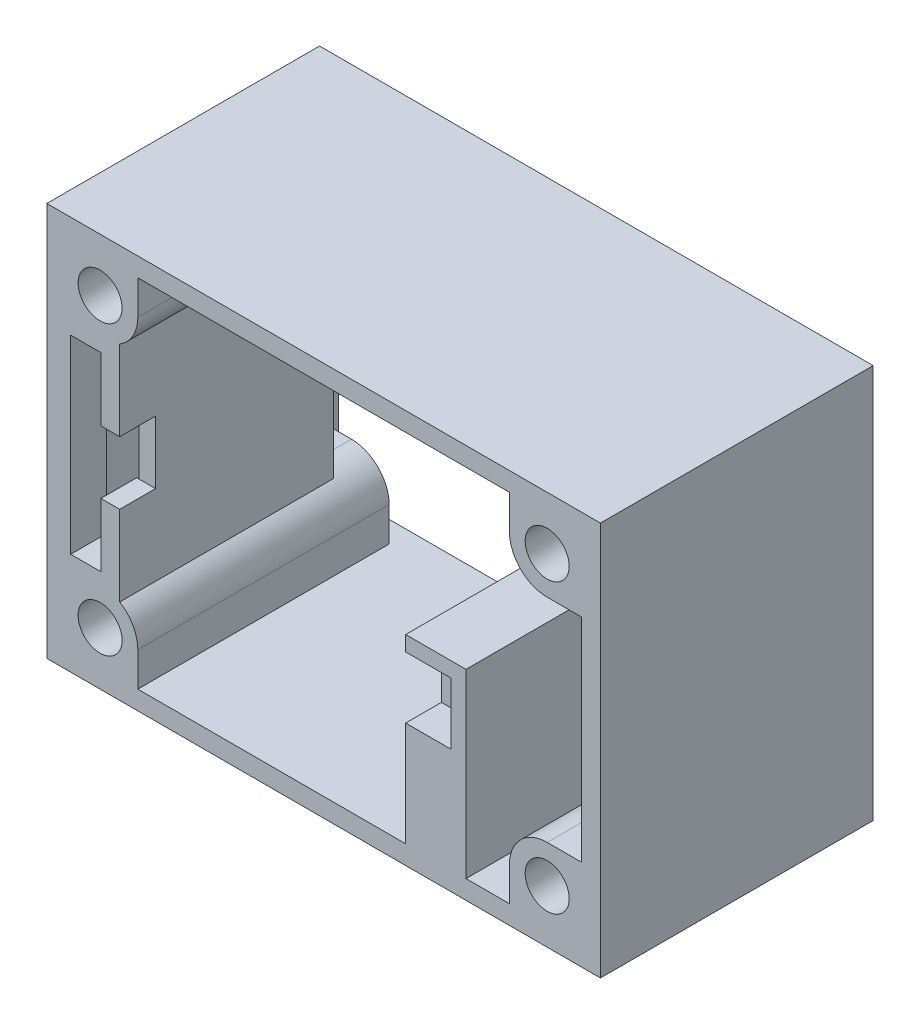
SolidWorks part; units mm, degrees
ref_plane "Front Plane" through (0, 0, 0) normal (0, 0, 1) x (1, 0, 0)
ref_plane "Top Plane" through (0, 0, 0) normal (0, 1, 0) x (1, 0, 0)
ref_plane "Right Plane" through (0, 0, 0) normal (1, 0, 0) x (0, 0, -1)
sketch "Sketch1" plane through (0, 0, 0) normal (0, 0, 1) x (1, 0, 0)
  line L0 (-20.325, 13.975) -> (-20.325, 14.175) construction
  line L1 (-22.025, -15.675) -> (22.025, -15.675)
  line L2 (-22.025, -15.675) -> (-22.025, 15.675)
  line L3 (-22.025, 15.675) -> (22.025, 15.675)
  line L4 (20.325, -13.975) -> (20.325, 13.975)
  line L5 (20.325, 13.975) -> (-20.325, 13.975)
  line L6 (-20.325, 13.975) -> (-20.325, -13.975)
  line L7 (-20.325, -13.975) -> (20.325, -13.975)
  line L8 (20.325, -13.975) -> (20.325, 13.975)
  line L9 (20.325, 13.975) -> (-20.325, 13.975)
  line L10 (-20.325, 13.975) -> (-20.325, -13.975)
  line L11 (-20.325, -13.975) -> (20.325, -13.975)
  line L12 (22.025, -15.675) -> (22.025, 15.675)
  line L13 (-22.025, -15.675) -> (22.025, 15.675) construction
  line L14 (-22.025, 15.675) -> (22.025, -15.675) construction
  line L15 (-20.325, 13.975) -> (-20.525, 13.975) construction
  line L16 (-14.7875, 11.45) -> (-14.7875, 14.175)
  line L17 (-17.7875, 8.45) -> (-20.525, 8.45)
  line L18 (0, 15.675) -> (0, -15.675) construction
  line L19 (-22.025, 0) -> (22.025, 0) construction
  line L20 (14.7875, 11.45) -> (14.7875, 14.175)
  line L21 (17.7875, 8.45) -> (20.525, 8.45)
  line L22 (17.7875, -8.45) -> (20.525, -8.45)
  line L23 (14.7875, -11.45) -> (14.7875, -14.175)
  line L24 (-14.7875, -11.45) -> (-14.7875, -14.175)
  line L25 (-17.7875, -8.45) -> (-20.525, -8.45)
  line L26 (-20.525, 14.175) -> (-22.025, 14.175) construction
  line L27 (20.525, -14.175) -> (-20.525, -14.175)
  line L28 (20.525, -14.175) -> (20.525, 14.175)
  line L29 (20.525, 14.175) -> (-20.525, 14.175)
  line L30 (-20.525, -14.175) -> (-20.525, 14.175)
  line L31 (20.525, -14.175) -> (-20.525, 14.175) construction
  line L32 (20.525, 14.175) -> (-20.525, -14.175) construction
  line L33 (-20.525, 14.175) -> (-20.525, 15.675) construction
  circle A0 centre (-17.7875, 11.45) radius 1.75
  circle A1 centre (17.7875, 11.45) radius 3
  circle A2 centre (17.7875, -11.45) radius 3
  circle A3 centre (-17.7875, -11.45) radius 3
  circle A4 centre (-17.7875, 11.45) radius 3
  circle A5 centre (17.7875, 11.45) radius 1.75
  circle A6 centre (17.7875, -11.45) radius 1.75
  circle A7 centre (-17.7875, -11.45) radius 1.75
  point P9 (0, 0)
  point P16 (0, 0)
  point P44 (-19.0562, -8.45)
  dimension "D2" = 3.5
  dimension "D4" = 6
  dimension "D3" = 1.5
  dimension "D5" = 0.2
  dimension "D1" = 0
extrude "Boss-Extrude1" add sketch "Sketch1" along normal blind 20 contours A4 L16 L9 | A4 L9 L16 L29 | L1 L12 L3 L2 A4 L29 A1 L28 A2 L27 A3 L30 | L29 A4 | A4 L29 L30 L10 L9 | A4 L9 L10 | L9 A4 L29 | L30 A4 | L10 A4 L30 | L9 A4 L10 A0 | A4 L30 L17 L10 | A4 L10 L17 | A1 L29 | L29 A1 L9 L8 L28 | L9 A1 L8 | A1 L8 L9 A5 | A1 L9 L29 | A1 L28 L8 | A1 L28 | L8 A1 L21 | L28 A1 L8 L21 | L20 A1 L9 | L9 A1 L29 L20 | A2 L28 L22 L8 | A2 L8 L22 | L8 A2 L11 A6 | L28 A2 | L28 A2 L8 | A2 L27 L28 L8 L11 | A2 L11 L8 | L11 A2 L27 | L27 A2 | A2 L23 L11 | A2 L11 L23 L27 | L27 A3 L11 L10 L30 | L11 A3 L10 | A3 L10 L30 | A3 L30 | L30 A3 L10 L25 | L10 A3 L25 | A3 L11 L10 A7 | A3 L11 L27 | A3 L27 | L24 A3 L11 | L11 A3 L27 L24 region at (-21.4843, 0, 0) region at (20.042, -13.6898, 0) region at (20.3461, -13.5127, 0) region at (19.8615, -13.508, 0) region at (20.4207, -11.45, 0) region at (17.7875, -14.0708, 0) region at (19.724, -8.8454, 0) region at (20.4289, -9.2415, 0) region at (20.6304, -11.45, 0) region at (15.5674, -14.0789, 0) region at (15.1778, -13.3764, 0) region at (17.7875, -14.2854, 0) region at (19.724, 8.8454, 0) region at (20.4289, 9.2415, 0) region at (-15.5674, -14.0789, 0) region at (-15.1778, -13.3764, 0) region at (19.1987, 8.8916, 0) region at (20.4207, 11.45, 0) region at (-17.7875, -14.0708, 0) region at (-17.7875, -13.8968, 0) region at (20.042, 13.6898, 0) region at (20.3461, 13.5127, 0) region at (20.6304, 11.45, 0) region at (15.1778, 13.3764, 0) region at (-19.2385, -14.0998, 0) region at (-20.042, -13.6898, 0) region at (-17.7875, -14.2854, 0) region at (-19.724, -8.8454, 0) region at (17.7875, 14.0708, 0) region at (15.5674, 14.0789, 0) region at (-20.4207, -11.45, 0) region at (-20.4289, -9.2415, 0) region at (17.7875, 14.2854, 0) region at (-15.1778, 13.3764, 0) region at (-15.5674, 14.0789, 0) region at (-20.6304, -11.45, 0) region at (-20.4289, 9.2415, 0) region at (-19.724, 8.8454, 0) region at (-15.2237, 12.8512, 0) region at (-17.7875, 14.0708, 0) region at (-20.4207, 11.45, 0) region at (-20.042, 13.6898, 0) region at (-19.8662, 13.9961, 0) region at (-17.7875, 14.2854, 0) region at (-20.6304, 11.45, 0)
sketch "Sketch2" plane through (0, 0, 0) normal (0, 0, -1) x (-1, 0, 0)
  line L0 (-14.7875, 14.175) -> (14.7875, 14.175) construction
  line L2 (-20.525, 14.175) -> (20.525, 14.175)
  line L3 (-20.525, 14.175) -> (-20.525, -14.175)
  line L4 (-20.525, -14.175) -> (20.525, -14.175)
  line L5 (-22.025, -15.675) -> (22.025, -15.675)
  line L6 (22.025, -15.675) -> (22.025, 15.675)
  line L7 (22.025, 15.675) -> (-22.025, 15.675)
  line L8 (-22.025, 15.675) -> (-22.025, -15.675)
  line L9 (-22.025, -15.675) -> (22.025, -15.675)
  line L10 (22.025, -15.675) -> (22.025, 15.675)
  line L11 (22.025, 15.675) -> (-22.025, 15.675)
  line L12 (-22.025, 15.675) -> (-22.025, -15.675)
  line L13 (20.525, 14.175) -> (20.525, -14.175)
  line L14 (-20.525, -8.45) -> (-20.525, 8.45) construction
  line L15 (20.525, -8.45) -> (20.525, 8.45) construction
  line L16 (-14.7875, -14.175) -> (14.7875, -14.175) construction
  line L17 (0, 14.175) -> (0, -14.175) construction
  line L18 (-20.525, 0) -> (20.525, 0) construction
  line L19 (1.5, -14.925) -> (1.5, -14.175)
  line L20 (-1.5, 14.925) -> (1.5, 14.925)
  line L21 (-1.5, 14.925) -> (-1.5, 14.175)
  line L22 (-1.5, 14.175) -> (1.5, 14.175)
  line L23 (1.5, 14.925) -> (1.5, 14.175)
  line L24 (-1.5, 14.925) -> (1.5, 14.175) construction
  line L25 (-1.5, 14.175) -> (1.5, 14.925) construction
  line L26 (-21.275, -1.5) -> (-20.525, -1.5)
  line L27 (-21.275, -1.5) -> (-21.275, 1.5)
  line L28 (-21.275, 1.5) -> (-20.525, 1.5)
  line L29 (-20.525, -1.5) -> (-20.525, 1.5)
  line L30 (-21.275, -1.5) -> (-20.525, 1.5) construction
  line L31 (-21.275, 1.5) -> (-20.525, -1.5) construction
  line L32 (-1.5, -14.925) -> (1.5, -14.925)
  line L33 (-1.5, -14.925) -> (-1.5, -14.175)
  line L34 (21.275, 1.5) -> (20.525, 1.5)
  line L35 (21.275, -1.5) -> (21.275, 1.5)
  line L36 (21.275, -1.5) -> (20.525, -1.5)
  point P20 (0, 14.55)
  point P25 (-20.9, 0)
  line M25 (-22.025, -15.675) -> (22.025, -15.675)
  line M26 (22.025, -15.675) -> (22.025, 15.675)
  line M27 (22.025, 15.675) -> (-22.025, 15.675)
  line M28 (-22.025, 15.675) -> (-22.025, -15.675)
  line M36 (20.525, 8.45) -> (20.525, -8.45)
  line M41 (-14.7875, 14.175) -> (14.7875, 14.175)
  line M62 (14.7875, -14.175) -> (-14.7875, -14.175)
  line M63 (-20.525, -8.45) -> (-20.525, 8.45)
  dimension "D2" = 0.75
  dimension "D3" = 3
  dimension "D1" = 0
extrude "Boss-Extrude2" add sketch "Sketch2" along normal blind 1.7 contours L35 L36 L13 L4 L19 L32 L33 L3 L26 L27 L28 L2 L21 L20 L23 L34 M28 M25 M26 M27 M36 M62 M63 M41 region at (21.4843, 0, 0)
ref_plane "Plane1" through (0, 0, 3) normal (0, 0, -1) x (-1, 0, 0)
sketch "Sketch3" plane through (0, 0, 3) normal (0, 0, -1) x (-1, 0, 0)
  line L0 (-20.525, 0) -> (20.525, 0) construction
  line L1 (-20.525, -1.5) -> (-20.525, 1.5) construction
  line L2 (20.525, -1.5) -> (20.525, 1.5) construction
  line L4 (-20.525, -8.45) -> (-20.525, 8.45) construction
  line L33 (20.525, 14.175) -> (20.525, 1.5) construction
  line L34 (16.225, -8.45) -> (20.525, -8.45)
  line L35 (16.225, -8.45) -> (16.225, 8.45)
  line L36 (16.225, 8.45) -> (20.525, 8.45)
  line L37 (20.525, -8.45) -> (20.525, 8.45)
  line L38 (16.225, -8.45) -> (20.525, 8.45) construction
  line L39 (16.225, 8.45) -> (20.525, -8.45) construction
  line L40 (17.7875, 8.45) -> (20.525, 8.45) construction
  line L41 (16.225, 8.45) -> (16.225, 8.889)
  line L42 (16.225, -8.45) -> (16.225, -8.889)
  line L43 (-8.925, 14.175) -> (-8.925, -14.175) construction
  line L44 (20.325, -7.75) -> (17.525, -7.75)
  line L45 (20.325, -7.75) -> (20.325, 7.75)
  line L46 (20.325, 7.75) -> (17.525, 7.75)
  line L47 (17.525, -7.75) -> (17.525, 7.75)
  line L48 (20.325, -7.75) -> (17.525, 7.75) construction
  line L49 (20.325, 7.75) -> (17.525, -7.75) construction
  line L50 (-20.525, 14.175) -> (-1.5, 14.175) construction
  line L51 (-1.5, -14.175) -> (-20.525, -14.175) construction
  line L52 (-10.325, -0.755) -> (-10.325, 0.245) construction
  line L53 (-6.525, 0.245) -> (-11.325, 0.245)
  line L54 (-6.525, 0.245) -> (-6.525, -14.175)
  line L55 (-6.525, -14.175) -> (-11.325, -14.175)
  line L56 (-11.325, 0.245) -> (-11.325, -14.175)
  line L57 (-6.525, 0.245) -> (-11.325, -14.175) construction
  line L58 (-6.525, -14.175) -> (-11.325, 0.245) construction
  line L59 (-10.325, -0.755) -> (-7.525, -0.755)
  line L60 (-10.325, -0.755) -> (-10.325, -6.055)
  line L61 (-10.325, -6.055) -> (-7.525, -6.055)
  line L62 (-7.525, -0.755) -> (-7.525, -6.055)
  line L63 (-10.325, -0.755) -> (-7.525, -6.055) construction
  line L64 (-10.325, -6.055) -> (-7.525, -0.755) construction
  line L65 (-10.325, -0.755) -> (-11.325, -0.755) construction
  arc A0 (-17.7875, 8.45) -> (-14.7875, 11.45) centre (-17.7875, 11.45) ccw construction
  arc A1 (-14.7875, -11.45) -> (-17.7875, -8.45) centre (-17.7875, -11.45) ccw construction
  arc A2 (-17.7875, 8.45) -> (-14.7875, 11.45) centre (-17.7875, 11.45) ccw
  arc A3 (-14.7875, -11.45) -> (-17.7875, -8.45) centre (-17.7875, -11.45) ccw
  arc A4 (14.7875, 11.45) -> (17.7875, 8.45) centre (17.7875, 11.45) ccw construction
  arc A5 (17.7875, -8.45) -> (14.7875, -11.45) centre (17.7875, -11.45) ccw construction
  arc A6 (17.7875, -8.45) -> (14.7875, -11.45) centre (17.7875, -11.45) ccw
  arc A7 (14.7875, 11.45) -> (17.7875, 8.45) centre (17.7875, 11.45) ccw
  point P41 (18.375, 0)
  point P58 (18.925, 0)
  point P71 (-8.925, -6.965)
  point P76 (-8.925, -3.405)
  dimension "D2" = 0.2
  dimension "D3" = 10.2
  dimension "D4" = 8.12
  dimension "D6" = 4.3
  dimension "D7" = 15.5
  dimension "D8" = 2.8
  dimension "D9" = 1
  dimension "D10" = 5.3
extrude "Boss-Extrude3" add sketch "Sketch3" against normal blind 14.15 contours A2 | A3 | L44 L47 L46 L37 L36 L35 L34 | A7 L41 L36 | A6 L34 L42 | L53 L56 L55 L54 L59 L62 L61 L60 region at (-16.3994, 0, 3) region at (-16.6097, -8.5799, 3) region at (-16.6097, 8.5799, 3) region at (8.925, -7.9366, 3)
sketch "Sketch4" plane through (0, 0, 17.15) normal (0, 0, 1) x (1, 0, 0)
  line L18 (11.325, 0.245) -> (6.525, 0.245)
  line L20 (-20.525, -8.45) -> (-17.7875, -8.45)
  line L21 (-16.225, -8.889) -> (-16.225, 8.889)
  line L22 (-17.7875, 8.45) -> (-20.525, 8.45)
  line L23 (-20.525, 8.45) -> (-20.525, -8.45)
  line L24 (-20.525, -8.45) -> (-17.7875, -8.45)
  line L25 (-16.225, -8.889) -> (-16.225, 8.889)
  line L26 (-17.7875, 8.45) -> (-20.525, 8.45)
  line L27 (-20.525, 8.45) -> (-20.525, -8.45)
  line L33 (-20.125, -7.55) -> (-17.725, -7.55)
  line L34 (-20.125, 7.55) -> (-20.125, -7.55)
  line L35 (11.325, -14.175) -> (11.325, 0.245)
  line L36 (6.525, -14.175) -> (11.325, -14.175)
  line L37 (6.525, 0.245) -> (6.525, -14.175)
  line L38 (11.325, 0.245) -> (6.525, 0.245)
  line L39 (11.325, -14.175) -> (11.325, 0.245)
  line L40 (6.525, -14.175) -> (11.325, -14.175)
  line L41 (6.525, 0.245) -> (6.525, -14.175)
  line L42 (-17.725, 7.55) -> (-20.125, 7.55)
  line L43 (-17.725, -7.55) -> (-17.725, 7.55)
  line L44 (-20.125, -7.55) -> (-17.725, -7.55)
  line L45 (-20.125, 7.55) -> (-20.125, -7.55)
  line L46 (7.725, -5.855) -> (10.125, -5.855)
  line L47 (7.725, -0.955) -> (7.725, -5.855)
  line L48 (10.125, -5.855) -> (10.125, -0.955)
  line L49 (10.125, -0.955) -> (7.725, -0.955)
  line L50 (7.725, -5.855) -> (10.125, -5.855)
  line L51 (7.725, -0.955) -> (7.725, -5.855)
  line L52 (10.125, -5.855) -> (10.125, -0.955)
  line L53 (10.125, -0.955) -> (7.725, -0.955)
  line L54 (-17.725, 7.55) -> (-20.125, 7.55)
  line L55 (-17.725, -7.55) -> (-17.725, 7.55)
  arc A2 (-16.225, -8.889) -> (-17.7875, -8.45) centre (-17.7875, -11.45) ccw
  arc A3 (-17.7875, 8.45) -> (-16.225, 8.889) centre (-17.7875, 11.45) ccw
  arc A4 (-16.225, -8.889) -> (-17.7875, -8.45) centre (-17.7875, -11.45) ccw
  arc A5 (-17.7875, 8.45) -> (-16.225, 8.889) centre (-17.7875, 11.45) ccw
  line M100 (-20.525, -8.45) -> (-17.7875, -8.45)
  arc M101 (-17.7875, -8.45) -> (-16.225, -8.889) centre (-17.7875, -11.45) cw
  line M102 (-16.225, -8.889) -> (-16.225, 8.889)
  arc M103 (-16.225, 8.889) -> (-17.7875, 8.45) centre (-17.7875, 11.45) cw
  line M104 (-17.7875, 8.45) -> (-20.525, 8.45)
  line M105 (-20.525, 8.45) -> (-20.525, -8.45)
  line M106 (-17.525, -7.75) -> (-20.325, -7.75)
  line M107 (-20.325, -7.75) -> (-20.325, 7.75)
  line M108 (-20.325, 7.75) -> (-17.525, 7.75)
  line M109 (-17.525, 7.75) -> (-17.525, -7.75)
  dimension "D1" = 0
  dimension "D2" = 0.2
  dimension "D3" = 0
  dimension "D4" = 0.2
extrude "Boss-Extrude4" add sketch "Sketch4" along normal up to surface (2.85 mm away) contours L38 L41 L40 L39 L53 L52 L50 L51 | M105 M100 M101 M102 M103 M104 M109 M106 M107 M108 | L55 L44 L45 L54 M106 M109 M108 M107 region at (8.925, -7.6937, 17.15) region at (-20.3421, 0, 17.15) region at (-18.925, -7.5925, 17.15) up to face at (0, 0, 20)
sketch "Sketch5" plane through (0, 0, 20) normal (0, 0, 1) x (1, 0, 0)
  line L0 (-16.225, 0) -> (-22.025, 0) construction
  line L1 (-16.225, -8.889) -> (-16.225, 8.889) construction
  line L2 (-22.025, -15.675) -> (-22.025, 15.675) construction
  line L3 (7.725, -3.405) -> (6.525, -3.405) construction
  line L4 (7.725, -0.955) -> (7.725, -5.855) construction
  line L5 (6.525, 0.245) -> (6.525, -14.175) construction
  line L6 (-17.725, -7.55) -> (-17.725, 7.55) construction
  line L7 (-17.725, -2.5) -> (-16.225, -2.5)
  line L8 (-17.725, -2.5) -> (-17.725, 2.5)
  line L9 (-17.725, 2.5) -> (-16.225, 2.5)
  line L10 (-16.225, -2.5) -> (-16.225, 2.5)
  line L11 (-17.725, -2.5) -> (-16.225, 2.5) construction
  line L12 (-17.725, 2.5) -> (-16.225, -2.5) construction
  line L14 (6.525, -5.855) -> (7.725, -5.855)
  line L15 (6.525, -5.855) -> (6.525, -0.955)
  line L16 (6.525, -0.955) -> (7.725, -0.955)
  line L17 (7.725, -5.855) -> (7.725, -0.955)
  line L18 (6.525, -5.855) -> (7.725, -0.955) construction
  line L19 (6.525, -0.955) -> (7.725, -5.855) construction
  point P12 (-16.975, 0)
  point P19 (7.125, -3.405)
  dimension "D1" = 5
extrude "Cut-Extrude1" cut sketch "Sketch5" against normal up to surface (2.85 mm away) up to face at (8.925, -3.405, 17.15)
